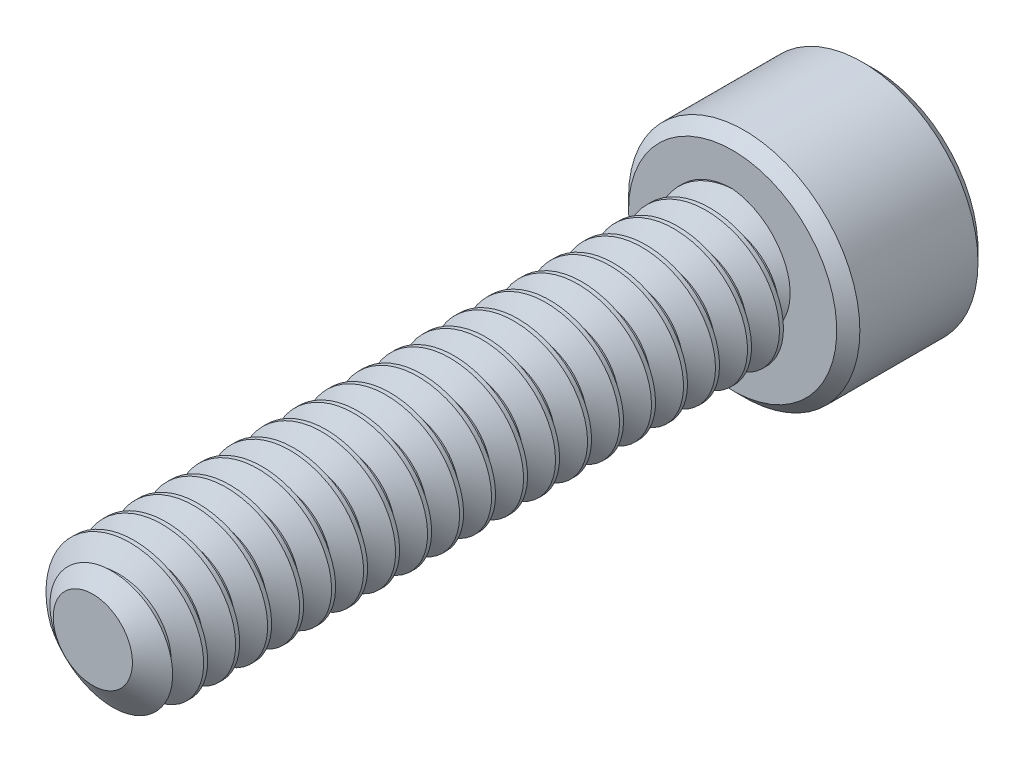
SolidWorks part; units mm, degrees
other "DetailItem1"
ref_plane "Front Plane" through (0, 0, 0) normal (0, 0, 1) x (1, 0, 0)
ref_plane "Top Plane" through (0, 0, 0) normal (0, 1, 0) x (1, 0, 0)
ref_plane "Right Plane" through (0, 0, 0) normal (1, 0, 0) x (0, 0, -1)
sketch "Sketch1" plane through (0, 0, 0) normal (0, 0, 1) x (1, 0, 0)
  circle A0 centre (0, 0) radius 1.7526
  dimension "OD" = 3.5052
extrude "Extrude1" add sketch "Sketch1" against normal blind 15.875
sketch "Sketch2" plane through (0, 0, 0) normal (0, 0, 1) x (1, 0, 0)
  circle A0 centre (0, 0) radius 1.7526 construction
  circle A1 centre (0, 0) radius 1.7526
curve "Helix/Spiral1" pitch 0.7937 height 16.6687 turns 21 parameters "pitch"=0.7937
sketch "Sketch3" plane through (0, 0, 0) normal (1, 0, 0) x (0, 0, -1)
  line L0 (-0.6945, 1.7526) -> (-0.3969, 1.237)
  line L1 (-0.3969, 1.237) -> (-0.2977, 1.237)
  line L2 (-0.2977, 1.237) -> (0, 1.7526)
  line L3 (-0.6945, 1.7526) -> (0, 1.7526)
  line L4 (-0.3473, 1.7526) -> (-0.3473, 1.237) construction
  line L5 (-0.5457, 1.4948) -> (-0.1488, 1.4948) construction
  line L6 (0, 1.7526) -> (0, -1.7526) construction
  dimension "D1" = 0.0992
  dimension "D2" = 0.3969
  dimension "D3" = 60
sweep "Cut-Sweep1" cut profiles "Sketch3" path "Helix/Spiral1"
sketch "Sketch4" plane through (0, 0, 0) normal (1, 0, 0) x (0, 0, -1)
  line L0 (0.5388, 1.7526) -> (0, 0.983)
  line L1 (0, 0.983) -> (0, 1.7526)
  line L2 (0.5388, 1.7526) -> (0, 1.7526)
  line L3 (-0.6945, 1.7526) -> (0, 1.7526) construction
  line L4 (0, 0) -> (7.0209, 0) construction
  dimension "D1" = 55
  dimension "D2" = 0.254
revolve "Cut-Revolve1" cut sketch "Sketch4" angle 360 about L4
sketch "Sketch6" plane through (0, 0, -15.875) normal (0, 0, -1) x (-1, 0, 0)
  circle A0 centre (0, 0) radius 2.8702
  dimension "head dia" = 5.7404
extrude "Extrude2" add sketch "Sketch6" along normal blind 3.5052
sketch "Sketch7" plane through (0, 0, -19.3802) normal (0, 0, -1) x (-1, 0, 0)
  line L1 (0, 1.604) -> (-1.3891, 0.802)
  line L2 (-1.3891, 0.802) -> (-1.3891, -0.802)
  line L3 (-1.3891, -0.802) -> (0, -1.604)
  line L4 (0, -1.604) -> (1.3891, -0.802)
  line L5 (1.3891, -0.802) -> (1.3891, 0.802)
  line L6 (1.3891, 0.802) -> (0, 1.604)
  circle A0 centre (0, 0) radius 1.3891 construction
  dimension "hex dia" = 2.7781
extrude "Cut-Extrude1" cut sketch "Sketch7" against normal blind 2.0836
sketch "Sketch8" plane through (0, 0, -19.3802) normal (0, 0, -1) x (-1, 0, 0)
  circle A0 centre (0, 0) radius 1.604
extrude "Cut-Extrude2" cut sketch "Sketch8" against normal through all draft 45
chamfer "Chamfer1" distance 0.287 angle 45 2 edges at (-2.8702, 0, -19.3802) (-2.8702, 0, -15.875)
sketch "Sketch10" plane through (0, 0, -15.875) normal (0, 0, 1) x (1, 0, 0)
  circle A1 centre (0, 0) radius 1.7526
  circle A2 centre (0, 0) radius 1.7526
  dimension "D1" = 0
ref_plane "Plane1" through (0, 0, -31.75) normal (0, 0, 1) x (1, 0, 0)
extrude "partial thread" [suppressed] add sketch "Sketch10" along normal up to surface (12.7 mm away) separate body
chamfer "Chamfer2" [suppressed] distance 0.0701 angle 45
combine bodies "Combine1" [suppressed] operation type add bodies to combine 107 108
sketch "Sketch9" plane through (0, 0, 0) normal (1, 0, 0) x (0, 0, -1)
  line L0 (0, 1.7526) -> (0, -1.7526) construction
  line L1 (1.9844, 1.7526) -> (1.9844, -1.7526) construction
  dimension "D1" = 1.9844
equation "\"D3@Helix/Spiral1\" = \"screw length@Extrude1\"+\"pitch@Helix/Spiral1\""
equation "\"D1@Sketch3\" = \"pitch@Helix/Spiral1\"*.125"
equation "\"D2@Sketch3\" = \"pitch@Helix/Spiral1\"*.5"
equation "\"D1@Cut-Extrude1\" = \"hex dia@Sketch7\"*.75"
equation "\"D1@Chamfer1\" = \"head dia@Sketch6\"*.05"
equation "\"D1@Sketch9\" = \"pitch@Helix/Spiral1\"*2.5"
equation "\"D1@Chamfer2\"=\"OD@Sketch1\"*.02"
